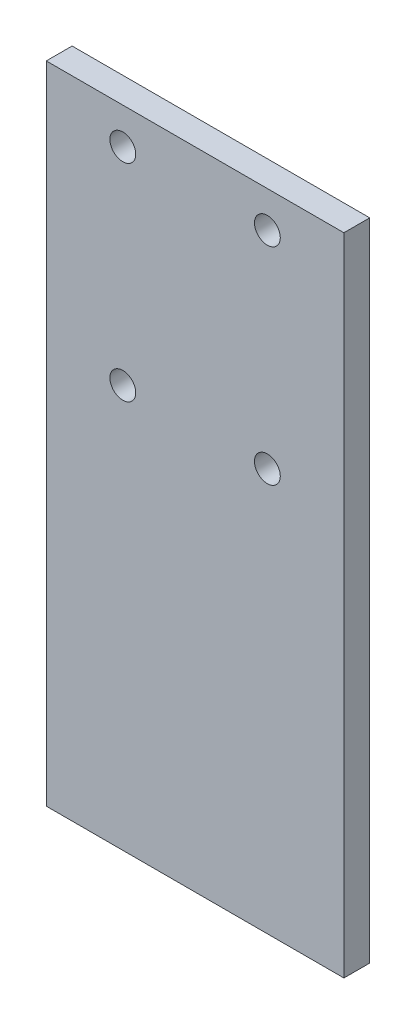
SolidWorks part; units mm, degrees
ref_plane "정면" through (0, 0, 0) normal (0, 0, 1) x (1, 0, 0)
ref_plane "윗면" through (0, 0, 0) normal (0, 1, 0) x (1, 0, 0)
ref_plane "우측면" through (0, 0, 0) normal (1, 0, 0) x (0, 0, -1)
sketch "스케치1" plane through (0, 0, 0) normal (0, 0, 1) x (1, 0, 0)
  line L1 (-28.82, 62.5) -> (28.82, 62.5)
  line L2 (-28.82, 62.5) -> (-28.82, -62.5)
  line L3 (-28.82, -62.5) -> (28.82, -62.5)
  line L4 (28.82, 62.5) -> (28.82, -62.5)
  line L5 (-28.82, 62.5) -> (28.82, -62.5) construction
  line L6 (-28.82, -62.5) -> (28.82, 62.5) construction
  point P0 (0, 0)
  dimension "D1" = 57.64
  dimension "D2" = 125
extrude "보스-돌출1" add sketch "스케치1" along normal blind 5
sketch "스케치2" plane through (0, 0, 5) normal (0, 0, 1) x (1, 0, 0)
  line L0 (28.82, 62.5) -> (-28.82, 62.5) construction
  circle A10 centre (-14, 55.5) radius 5.8
  circle A11 centre (-14, 55.5) radius 2.5
  circle A12 centre (14, 55.5) radius 5.8
  circle A13 centre (14, 55.5) radius 2.5
  circle A14 centre (-14, 15.5) radius 5.8
  circle A15 centre (-14, 15.5) radius 2.5
  circle A16 centre (14, 15.5) radius 5.8
  circle A17 centre (14, 15.5) radius 2.5
  point P15 (0, 0)
  point P17 (0, 0)
  dimension "D3" = 5
  dimension "D4" = 11.6
  dimension "D5" = 5
  dimension "D8" = 11.6
  dimension "D9" = 11.6
  dimension "D10" = 40
  dimension "D11" = 7
  dimension "D12" = 14
  dimension "D13" = 14
  dimension "D2" = 11.6
  dimension "D6" = 5
  dimension "D7" = 5
  dimension "D14" = 7
  dimension "D15" = 14
  dimension "D16" = 14
  dimension "D17" = 40
extrude "컷-돌출1" cut sketch "스케치2" against normal blind 5 contours A13 | A17 | A15 | A11 region at (14, 55.5, 5) region at (-14, 15.5, 5) region at (14, 15.5, 5)
